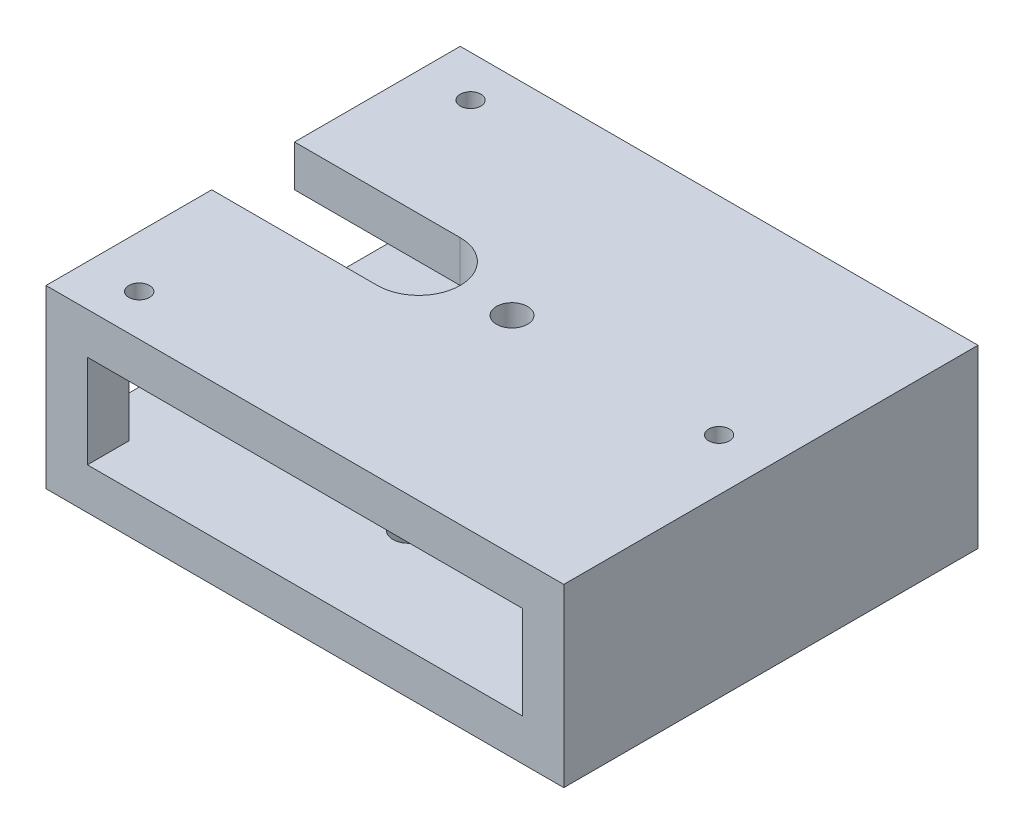
SolidWorks part; units mm, degrees
ref_plane "Front Plane" through (0, 0, 0) normal (0, 0, 1) x (1, 0, 0)
ref_plane "Top Plane" through (0, 0, 0) normal (0, 1, 0) x (1, 0, 0)
ref_plane "Right Plane" through (0, 0, 0) normal (1, 0, 0) x (0, 0, -1)
sketch "Sketch1" plane through (0, 0, 0) normal (0, 1, 0) x (1, 0, 0)
  line L1 (-125, 100) -> (125, 100)
  line L2 (-125, 100) -> (-125, -100)
  line L3 (-125, -100) -> (125, -100)
  line L4 (125, 100) -> (125, -100)
  line L5 (-125, 100) -> (125, -100) construction
  line L6 (-125, -100) -> (125, 100) construction
  circle A0 centre (0, 0) radius 75 construction
  point P0 (0, 0)
  dimension "D3" = 150
  dimension "D1" = 200
  dimension "D2" = 250
extrude "Boss-Extrude1" add sketch "Sketch1" along normal blind 20
extrude "Boss-Extrude2" add sketch "Sketch1<2>" along normal blind 20 from offset 65 separate body
sketch "Sketch1<2>" plane through (0, 0, 0) normal (0, 1, 0) x (1, 0, 0) same geometry as "Sketch1"
sketch "Sketch2" plane through (0, 20, 0) normal (0, 1, 0) x (1, 0, 0)
  line L0 (-12.3559, 0) -> (17.2099, 0) construction
  line L1 (-125, -100) -> (-105, -100)
  line L2 (-125, -100) -> (-125, -80)
  line L3 (-125, -80) -> (-105, -80)
  line L4 (-105, -100) -> (-105, -80)
  line L5 (0, 20.9608) -> (0, -15.2242) construction
  line L6 (-125, 100) -> (-105, 100)
  line L7 (-125, 100) -> (-125, 80)
  line L8 (-105, 100) -> (-105, 80)
  line L9 (-125, 80) -> (-105, 80)
  line L10 (125, 80) -> (105, 80)
  line L11 (105, 100) -> (105, 80)
  line L12 (125, 100) -> (125, 80)
  line L13 (125, 100) -> (105, 100)
  line L14 (105, -100) -> (105, -80)
  line L15 (125, -80) -> (105, -80)
  line L16 (125, -100) -> (125, -80)
  line L17 (125, -100) -> (105, -100)
  dimension "D1" = 20
  dimension "D2" = 20
extrude "Boss-Extrude3" add sketch "Sketch2" along normal blind 45
sketch "Sketch4" plane through (0, 85, 0) normal (0, 1, 0) x (1, 0, 0)
  line L0 (125, 100) -> (125, -100) construction
  line L1 (-125, -100) -> (125, 100) construction
  line L2 (-125, 100) -> (125, -100) construction
  line L3 (-125, 100) -> (-125, -100) construction
  circle A0 centre (100, 0) radius 5
  circle A1 centre (-100, -80) radius 5
  circle A2 centre (-100, 80) radius 5
  dimension "D1" = 10
  dimension "D2" = 25
  dimension "D3" = 25
extrude "Cut-Extrude1" cut sketch "Sketch4" against normal blind 10
sketch "Sketch5" plane through (0, 85, 0) normal (0, 1, 0) x (1, 0, 0)
  circle A0 centre (0, 0) radius 7.5
  dimension "D1" = 15
extrude "Cut-Extrude2" cut sketch "Sketch5" against normal blind 75
sketch "Sketch6" plane through (0, 85, 0) normal (0, 1, 0) x (1, 0, 0)
  line L0 (0, 0) -> (-39.274, 0) construction
  line L1 (-125, 100) -> (125, -100) construction
  line L2 (-125, 20) -> (-45, 20)
  line L3 (-125, 100) -> (-125, -100) construction
  line L4 (-125, -20) -> (-45, -20)
  line L5 (-125, 20) -> (-125, -20)
  arc A0 (-45, 20) -> (-45, -20) centre (-45, 0) cw
  dimension "D1" = 40
  dimension "D2" = 80
extrude "Cut-Extrude3" cut sketch "Sketch6" against normal through all and the other way through all
sketch "Sketch7" plane through (0, 0, 0) normal (0, -1, 0) x (1, 0, 0)
  circle A0 centre (0, 0) radius 75
  circle A1 centre (0, 0) radius 50 construction
  circle A2 centre (0, 50) radius 7.5
  dimension "D1" = 150
  dimension "D2" = 100
  dimension "D3" = 15
extrude "Cut-Extrude4" cut sketch "Sketch7" against normal up to surface (20 mm away) contours A2 region at (0, 0, 50) up to face at (-20, 20, 0)
sketch "Sketch8" plane through (125, 0, 0) normal (1, 0, 0) x (0, 0, -1)
  line L0 (80, 65) -> (80, 20) construction
  line L1 (-80, 20) -> (80, 20) construction
  line L2 (-80, 65) -> (-80, 20) construction
  line L3 (-80, 65) -> (80, 65) construction
  line L4 (80, 65) -> (80, 20)
  line L5 (-80, 20) -> (80, 20)
  line L6 (-80, 65) -> (-80, 20)
  line L7 (-80, 65) -> (80, 65)
extrude "Boss-Extrude4" add sketch "Sketch8" against normal blind 5
